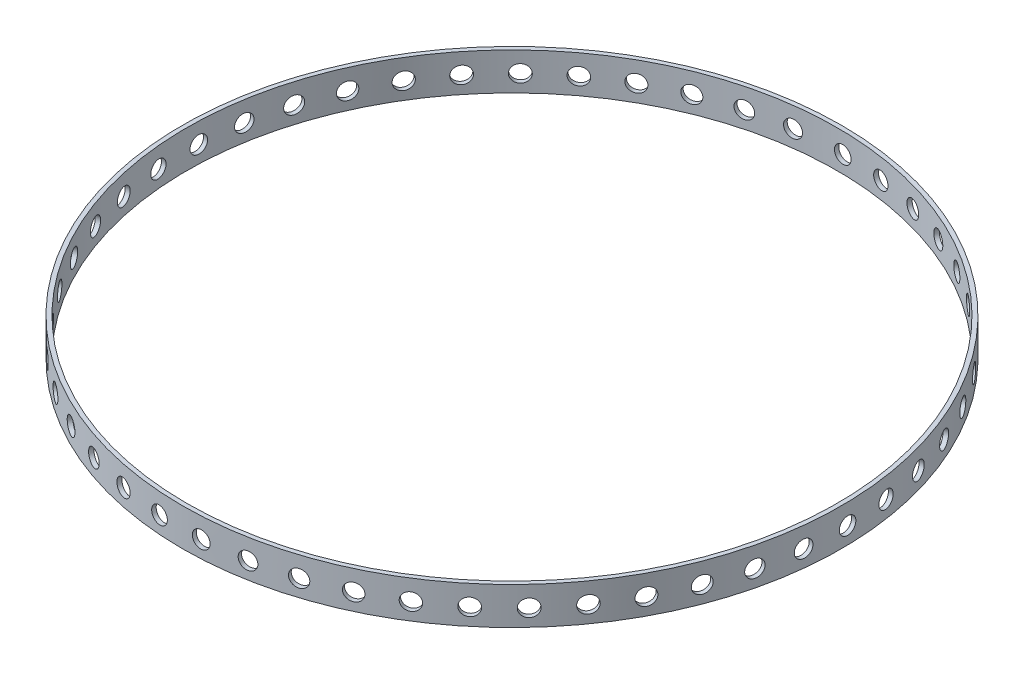
SolidWorks part; units mm, degrees
material "ABS PC"
ref_plane "Front" through (0, 0, 0) normal (0, 0, 1) x (1, 0, 0)
ref_plane "Top" through (0, 0, 0) normal (0, 1, 0) x (1, 0, 0)
ref_plane "Right" through (0, 0, 0) normal (1, 0, 0) x (0, 0, -1)
sketch "Sketch1" plane through (0, 0, 0) normal (0, 1, 0) x (1, 0, 0)
  circle A0 centre (0, 0) radius 96
  circle A1 centre (0, 0) radius 97.25
  dimension "D1" = 194.5
  dimension "D2" = 192
extrude "Boss-Extrude1" add sketch "Sketch1" along normal blind 11
sketch "Sketch2" plane through (0, 0, 0) normal (0, 0, 1) x (1, 0, 0)
  line L0 (0, 0) -> (0, 5) construction
  circle A0 centre (0, 5) radius 2.5
  dimension "D2" = 5
  dimension "D1" = 5
extrude "Cut-Extrude1" cut sketch "Sketch2" against normal blind 500
pattern_circular "CirPattern9" count 50 over 359 about axis through (0, 11, 0) along (0, 1, 0) of "Cut-Extrude1", "Boss-Extrude1"
